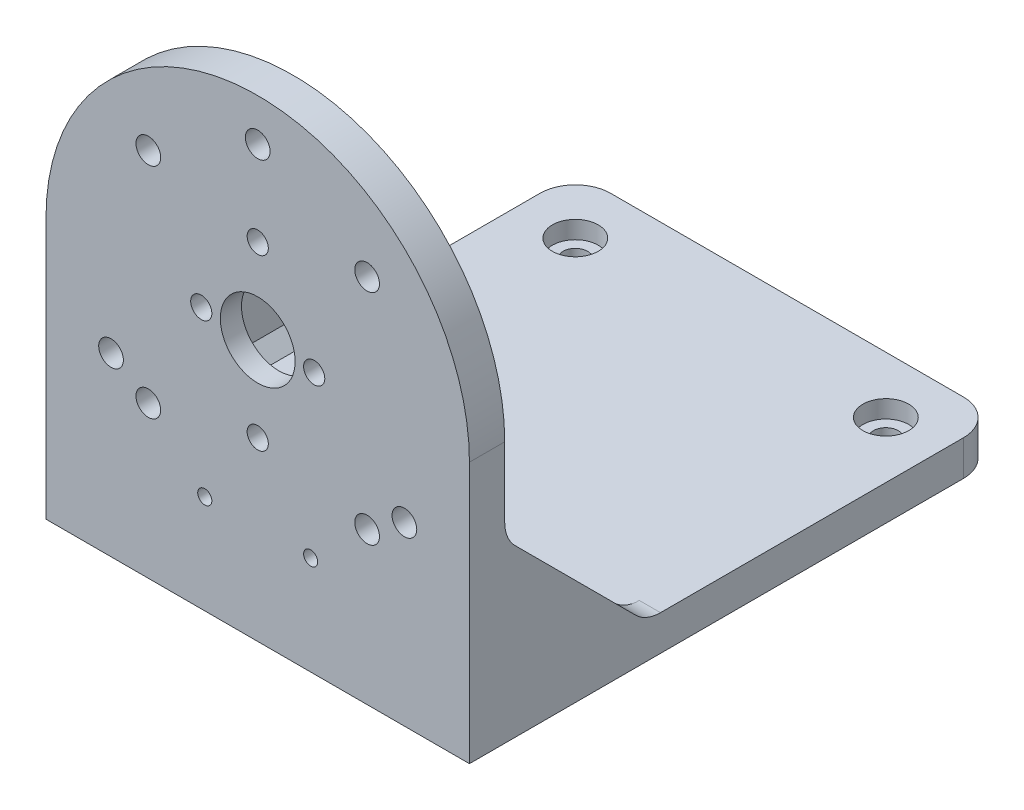
SolidWorks part; units mm, degrees
ref_plane "Plano frontal" through (0, 0, 0) normal (0, 0, 1) x (1, 0, 0)
ref_plane "Plano superior" through (0, 0, 0) normal (0, 1, 0) x (1, 0, 0)
ref_plane "Plano direito" through (0, 0, 0) normal (1, 0, 0) x (0, 0, -1)
sketch "Esboço1" plane through (0, 0, 0) normal (0, 0, 1) x (1, 0, 0)
  line L0 (-30, 0) -> (-30, -37)
  line L1 (-30, -37) -> (30, -37)
  line L2 (30, -37) -> (30, 0)
  circle A0 centre (0, 0) radius 5.3
  arc A1 (30, 0) -> (-30, 0) centre (0, 0) ccw
  dimension "D1" = 10.6
  dimension "D2" = 60
  dimension "D3" = 37
extrude "Ressalto-extrusão1" add sketch "Esboço1" along normal blind 5
sketch "Esboço2" plane through (0, 0, 0) normal (0, 0, -1) x (-1, 0, 0)
  line L0 (30, 0) -> (30, -37) construction
  line L1 (-30, -37) -> (30, -37)
  line L2 (-30, -37) -> (-30, -32)
  line L3 (-30, -32) -> (30, -32)
  line L4 (30, -37) -> (30, -32)
  dimension "D1" = 5
extrude "Ressalto-extrusão2" add sketch "Esboço2" along normal blind 70
sketch "Esboço5" plane through (0, 0, 0) normal (0, 0, -1) x (-1, 0, 0)
  circle A0 centre (0, 0) radius 16
  dimension "D1" = 32
extrude "Corte-extrusão2" cut sketch "Esboço5" against normal blind 2
fillet "Filete1" radius 5 2 edges at (-30, -34.5, -70) (30, -34.5, -70)
sketch "Esboço3" plane through (0, 0, 5) normal (0, 0, 1) x (1, 0, 0)
  circle A0 centre (0, 24) radius 1.75
  circle A1 centre (0, 0) radius 5.3 construction
  circle A2 centre (20.7846, -12) radius 1.75
  circle A3 centre (-20.7846, -12) radius 1.75
  point P11 (0, 0)
  dimension "D1" = 24
  dimension "D2" = 3.5
  dimension "D3" = 3
extrude "Corte-extrusão1" cut sketch "Esboço3" against normal through all
sketch "Esboço4" plane through (-30, 0, 0) normal (-1, 0, 0) x (0, 0, 1)
  line L0 (-20, -32) -> (0, -12)
  line L1 (-65, -32) -> (0, -32) construction
  line L2 (0, 0) -> (0, -32) construction
  line L3 (0, -12) -> (0, -32)
  line L4 (0, -32) -> (-20, -32)
  dimension "D1" = 20
  dimension "D2" = 20
extrude "Ressalto-extrusão3" add sketch "Esboço4" against normal blind 3
mirror "Espelhar1" about plane through (0, 0, 0) normal (1, 0, 0) of "Ressalto-extrusão3"
fillet "Filete2" radius 5 4 edges at (-28.5, -12, 0) (-28.5, -32, -20) (28.5, -32, -20) (28.5, -12, 0)
sketch "Esboço6" plane through (0, 0, 5) normal (0, 0, 1) x (1, 0, 0)
  line L0 (0, 5.3) -> (0, -5.3) construction
  circle A9 centre (-8, 0) radius 1.5
  circle A12 centre (0, 0) radius 5.3 construction
  circle A13 centre (8, 0) radius 1.5
  dimension "D1" = 8
  dimension "D2" = 3
extrude "Corte-extrusão3" cut sketch "Esboço6" against normal through all
sketch "Esboço8" plane through (0, 0, 5) normal (0, 0, 1) x (1, 0, 0)
  line L0 (-5.3, 0) -> (5.3, 0) construction
  circle A0 centre (0, 12) radius 1.5
  circle A1 centre (0, 0) radius 5.3 construction
  circle A2 centre (0, -12) radius 1.5
  dimension "D1" = 12
  dimension "D2" = 3
extrude "Corte-extrusão4" cut sketch "Esboço8" against normal through all
sketch "Esboço9" plane through (0, 0, 5) normal (0, 0, 1) x (1, 0, 0)
  circle A0 centre (-15.5, 15.5) radius 1.75
  circle A1 centre (15.5, 15.5) radius 1.75
  circle A2 centre (15.5, -15.5) radius 1.75
  circle A3 centre (-15.5, -15.5) radius 1.75
  point P12 (0, 0)
  dimension "D1" = 15.5
  dimension "D2" = 15.5
  dimension "D3" = 3.5
extrude "Corte-extrusão5" cut sketch "Esboço9" against normal through all
sketch "Esboço10" plane through (0, -32, 0) normal (0, 1, 0) x (1, 0, 0)
  line L0 (-25, 70) -> (25, 70) construction
  line L1 (-30, 65) -> (-30, 22.0711) construction
  line L2 (30, 65) -> (30, 22.0711) construction
  circle A0 centre (0, 8) radius 1.75
  circle A1 centre (-22, 62) radius 1.75
  circle A2 centre (22, 62) radius 1.75
  dimension "D1" = 3.5
  dimension "D2" = 3.5
  dimension "D3" = 3.5
  dimension "D4" = 8
  dimension "D5" = 8
  dimension "D6" = 8
  dimension "D7" = 8
  dimension "D8" = 8
extrude "Corte-extrusão6" cut sketch "Esboço10" against normal through all
sketch "Esboço11" plane through (0, -32, 0) normal (0, 1, 0) x (1, 0, 0)
  circle A0 centre (-22, 62) radius 3.25
  circle A1 centre (22, 62) radius 3.25
  circle A2 centre (0, 8) radius 3.25
  dimension "D1" = 6.5
  dimension "D2" = 6.5
  dimension "D3" = 6.5
extrude "Corte-extrusão7" cut sketch "Esboço11" against normal blind 2.5
sketch "Esboço13" plane through (0, -37, 0) normal (0, 1, 0) x (1, 0, 0)
  line L5 (-25, 70) -> (25, 70) construction
  line L6 (0, 70) -> (0, -5) construction
  line L7 (-30, -5) -> (30, -5) construction
  line L8 (-43, 32) -> (-43, 12)
  line L9 (-30, 12) -> (-43, 12)
  line L10 (-30, 32) -> (-30, 12)
  line L11 (-30, 32) -> (-43, 32)
  circle A2 centre (-36.5, 18) radius 1.25
  circle A3 centre (-36.5, 26) radius 1.25
  dimension "D4" = 6
  dimension "D5" = 8
  dimension "D6" = 2.5
  dimension "D7" = 2.5
  dimension "D1" = 20
  dimension "D2" = 38
  dimension "D3" = 13
extrude "Ressalto-extrusão4" add sketch "Esboço13" along normal blind 18
sketch "Esboço18" plane through (0, 0, 5) normal (0, 0, 1) x (1, 0, 0)
  circle A0 centre (-7.5, -23) radius 1
  circle A1 centre (7.5, -23) radius 1
  circle A2 centre (0, 0) radius 5.3 construction
  dimension "D1" = 7.5
  dimension "D2" = 7.5
  dimension "D3" = 0
  dimension "D4" = 23
  dimension "D5" = 2
  dimension "D6" = 2
extrude "Corte-extrusão9" cut sketch "Esboço18" against normal blind 4
chamfer "Chanfro1" distance 2 angle 45 1 edges at (-30, -32, -27.0355)
